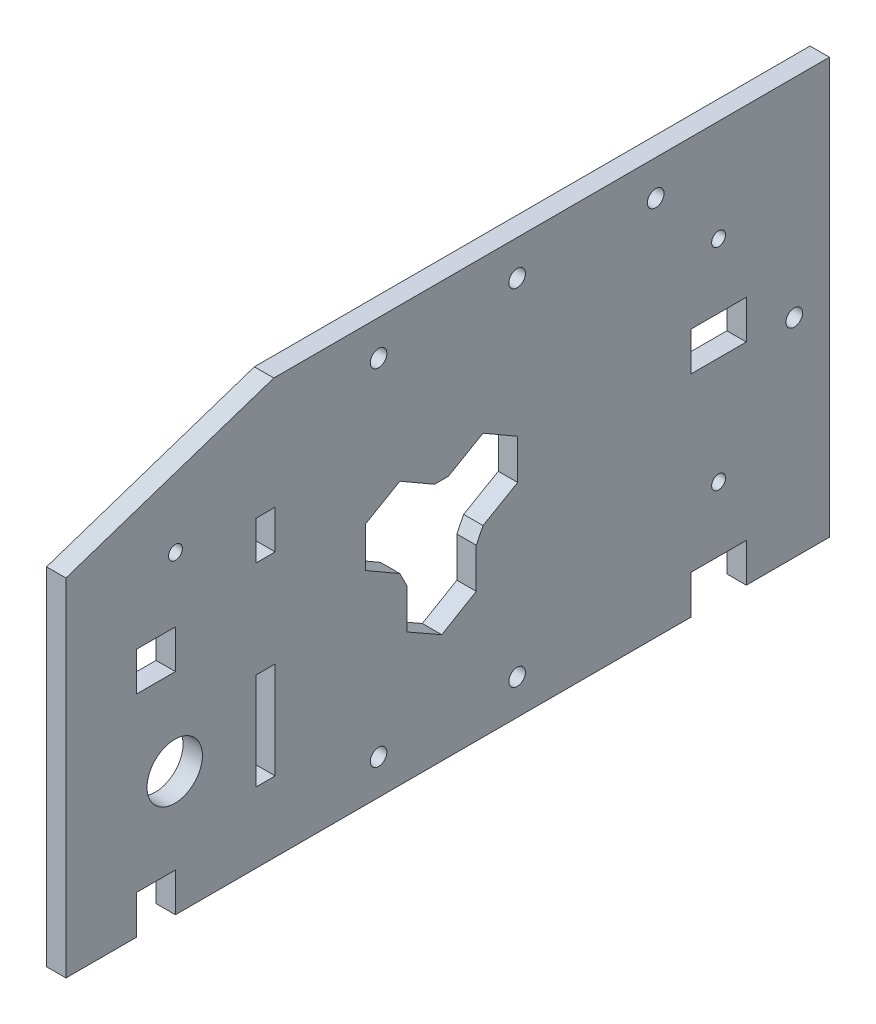
SolidWorks part; units mm, degrees
other "Markup1"
sketch "Sketch2" plane through (14, 75, 158) normal (0.4984, 0.5123, 0.6994) x (0.8144, 0, -0.5803)
sketch "Sketch3" plane through (14, 75, 158) normal (0.4984, 0.5123, 0.6994) x (0.8144, 0, -0.5803)
sketch "Sketch4" plane through (14, 75, 158) normal (0.4984, 0.5123, 0.6994) x (0.8144, 0, -0.5803)
sketch "Sketch5" plane through (14, 75, 158) normal (0.4984, 0.5123, 0.6994) x (0.8144, 0, -0.5803)
sketch "Sketch7" plane through (14, 75, 158) normal (0.4984, 0.5123, 0.6994) x (0.8144, 0, -0.5803)
sketch "Sketch8" plane through (7, 75, 158) normal (0.4984, 0.5123, 0.6994) x (0.8144, 0, -0.5803)
sketch "Sketch9" [suppressed] plane through (7, 75, 158) normal (0.4984, 0.5123, 0.6994) x (0.8144, 0, -0.5803)
sketch "Sketch11" [suppressed] plane through (7, 75, 158) normal (0.4984, 0.5123, 0.6994) x (0.8144, 0, -0.5803)
sketch "Sketch12" plane through (7, 75, 158) normal (0.4984, 0.5123, 0.6994) x (0.8144, 0, -0.5803)
sketch "Sketch13" plane through (7, 75, 158) normal (0.4984, 0.5123, 0.6994) x (0.8144, 0, -0.5803)
sketch "Sketch14" plane through (7, 75, 158) normal (0.4984, 0.5123, 0.6994) x (0.8144, 0, -0.5803)
sketch "Sketch17" plane through (7, 75, 158) normal (0.4984, 0.5123, 0.6994) x (0.8144, 0, -0.5803)
sketch "Sketch18" plane through (7, 75, 158) normal (0.4984, 0.5123, 0.6994) x (0.8144, 0, -0.5803)
sketch "Sketch19" plane through (7, 75, 158) normal (0.4984, 0.5123, 0.6994) x (0.8144, 0, -0.5803)
sketch "Sketch20" plane through (7, 75, 158) normal (0.4984, 0.5123, 0.6994) x (0.8144, 0, -0.5803)
sketch "Sketch21" plane through (7, 75, 158) normal (0.4984, 0.5123, 0.6994) x (0.8144, 0, -0.5803)
sketch "Sketch22" plane through (7, 75, 158) normal (0.4984, 0.5123, 0.6994) x (0.8144, 0, -0.5803)
material "Maple"
ref_plane "Front Plane" through (0, 0, 0) normal (0, 0, 1) x (1, 0, 0)
ref_plane "Top Plane" through (0, 0, 0) normal (0, 1, 0) x (1, 0, 0)
ref_plane "Right Plane" through (0, 0, 0) normal (1, 0, 0) x (0, 0, -1)
sketch "Sketch1" plane through (0, 0, 0) normal (1, 0, 0) x (0, 0, -1)
  line L1 (-118.5, -75) -> (67.5, -75)
  line L3 (-83, 75) -> (117.5, 75)
  line L4 (117.5, -75) -> (117.5, 75)
  line L9 (-132.5, -61) -> (-118.5, -61)
  line L10 (-118.5, -75) -> (-118.5, -61)
  line L11 (-132.5, 15) -> (-118.5, 15)
  line L13 (-132.5, 1) -> (-118.5, 1)
  line L14 (-118.5, 15) -> (-118.5, 1)
  line L18 (87.5, -75) -> (117.5, -75)
  line L20 (87.5, -75) -> (87.5, -61)
  line L21 (87.5, -61) -> (67.5, -61)
  line L22 (67.5, -75) -> (67.5, -61)
  line L23 (87.5, 1) -> (67.5, 1)
  line L24 (87.5, 1) -> (87.5, 15)
  line L25 (87.5, 15) -> (67.5, 15)
  line L26 (67.5, 1) -> (67.5, 15)
  line L27 (-22.3973, -35.5167) -> (-9.9486, -28.2116)
  line L28 (-9.9486, -28.2116) -> (-9.9486, -13.7778)
  line L31 (-34.9486, -13.9557) -> (-34.9486, -28.3895)
  line L32 (-34.9486, -28.3895) -> (-22.3973, -35.5167)
  line L35 (-25, 12.7831) -> (-37.5, 20)
  line L36 (-37.5, 20) -> (-50, 12.7831)
  line L37 (-50, 12.7831) -> (-50, -1.6506)
  line L38 (-50, -1.6506) -> (-37.5, -8.8675)
  line L39 (-7.5, -8.8675) -> (5, -1.6506)
  line L40 (5, -1.6506) -> (5, 12.7831)
  line L41 (5, 12.7831) -> (-7.5, 20)
  line L42 (-7.5, 20) -> (-20, 12.7831)
  line L47 (-132.5, 15) -> (-132.5, 1)
  line L48 (-132.5, -75) -> (-158, -75)
  line L49 (-158, 50) -> (-158, -75)
  line L50 (-132.5, -61) -> (-132.5, -75)
  line L51 (-83, 75) -> (-158, 50)
  line L52 (-82.5, 20.4) -> (-89.5, 20.4)
  line L53 (-82.5, 20.4) -> (-82.5, 34.4)
  line L54 (-82.5, 34.4) -> (-89.5, 34.4)
  line L55 (-89.5, 20.4) -> (-89.5, 34.4)
  line L56 (-37.5, -8.8675) -> (-34.9486, -13.9557)
  line L57 (-9.9486, -13.7778) -> (-7.5, -8.8675)
  line L58 (-20, 12.7831) -> (-25, 12.7831)
  line L60 (-89.5, -14.6) -> (-82.5, -14.6)
  line L61 (-89.5, -14.6) -> (-89.5, -49.6)
  line L62 (-89.5, -49.6) -> (-82.5, -49.6)
  line L63 (-82.5, -14.6) -> (-82.5, -49.6)
  circle A0 centre (-118.75, -30.05) radius 10
  circle A1 centre (77.5, 38.27) radius 2.5
  circle A2 centre (-118.5, 38.27) radius 2.5
  circle A4 centre (77.5, -37.73) radius 2.5
  point P0 (0, 0)
  point P56 (77.5, 15)
  dimension "D7" = 20
  dimension "D9" = 44.95
  dimension "D13" = 39.5
  dimension "D21" = 5
  dimension "D1" = 150
  dimension "D3" = 14
  dimension "D4" = 76
  dimension "D5" = 117.5
  dimension "D6" = 1
  dimension "D8" = 39.25
  dimension "D10" = 206
  dimension "D11" = 20
  dimension "D12" = 55
  dimension "D14" = 29
  dimension "D15" = 25
  dimension "D16" = 5.4
  dimension "D17" = 35
  dimension "D18" = 155
  dimension "D19" = 35
  dimension "D20" = 275.5
  dimension "D22" = 23.27
  dimension "D23" = 7
  dimension "D24" = 25
  dimension "D25" = 75
  dimension "D26" = 23.27
extrude "Boss-Extrude1" add sketch "Sketch1" along normal blind 7
sketch "Sketch6" [suppressed] plane through (7, 0, 0) normal (1, 0, 0) x (0, 0, -1)
  line L1 (-50, 15) -> (15, 15)
  line L2 (-50, 15) -> (-50, -50)
  line L3 (-50, -50) -> (15, -50)
  line L4 (15, 15) -> (15, -50)
  dimension "D1" = 15
  dimension "D2" = 15
  dimension "D3" = 65
extrude "Cut-Extrude1" [suppressed] cut sketch "Sketch6" against normal through all
sketch "Sketch15" plane through (7, 0, 0) normal (1, 0, 0) x (0, 0, -1)
  line L0 (117.5, -75) -> (117.5, 75) construction
  line L2 (-118.5, -75) -> (67.5, -75) construction
  line L3 (117.5, 75) -> (-83, 75) construction
  point P0 (104.8, 0)
  point P2 (54.8, 62.3)
  point P4 (-45.2, -62.3)
  point P5 (4.8, -62.3)
  point P7 (4.8, 62.3)
  point P21 (-45.2, 62.3)
  dimension "D1" = 12.7
  dimension "D2" = 50
  dimension "D3" = 12.7
  dimension "D4" = 50
  dimension "D5" = 50
  dimension "D6" = 12.7
hole_wizard "Ø6.0 (6) Diameter Hole1" positions "3DSketch1" profile "Sketch16" hole size "Ø6.0" standard "ANSI Metric" end condition through all
sketch3d "3DSketch1"
  point P3 (7, -62.3, -4.8)
  point P12 (7, 0, -104.8)
  point P18 (7, 62.3, -54.8)
  point P21 (7, 62.3, -4.8)
  point P30 (7, 62.3, 45.2)
  point P33 (7, -62.3, 45.2)
sketch "Sketch16" plane through (7, -62.3, -4.8) normal (0, 1, 0) x (0, 0, -1)
  line L0 (0, 0) -> (0, 7)
  line L1 (0, 7) -> (3, 7)
  line L2 (3, 7) -> (3, 0)
  line L5 (3, 0) -> (0, 0)
  line L11 (0, -6.35) -> (0, 107.95) construction
  dimension "Thru Hole Dia." = 6
  dimension "Thru Hole Depth" = 7
